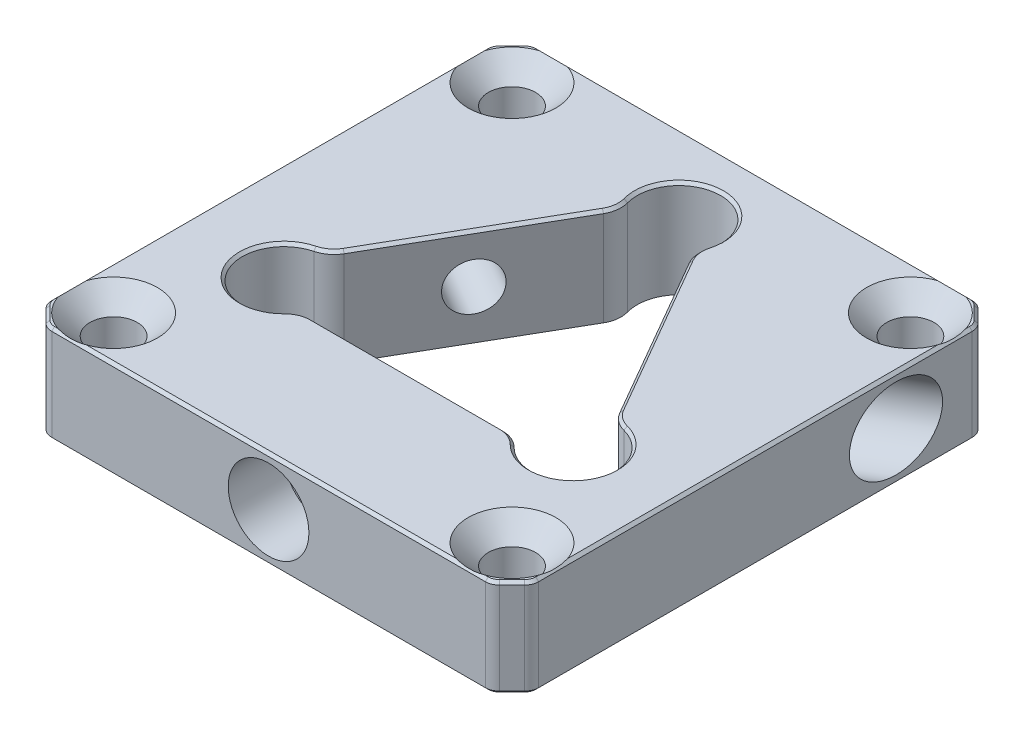
SolidWorks part; units mm, degrees
material "6061 合金"
ref_plane "前视基准面" through (0, 0, 0) normal (0, 0, 1) x (1, 0, 0)
ref_plane "上视基准面" through (0, 0, 0) normal (0, 1, 0) x (1, 0, 0)
ref_plane "右视基准面" through (0, 0, 0) normal (1, 0, 0) x (0, 0, -1)
sketch "草图36" plane through (0, 0, 0) normal (0, 1, 0) x (1, 0, 0)
  line L1 (-17.5, 17.5) -> (17.5, 17.5)
  line L2 (-17.5, 17.5) -> (-17.5, -17.5)
  line L3 (-17.5, -17.5) -> (17.5, -17.5)
  line L4 (17.5, 17.5) -> (17.5, -17.5)
  line L5 (-17.5, 17.5) -> (17.5, -17.5) construction
  line L6 (-17.5, -17.5) -> (17.5, 17.5) construction
  point P0 (0, 0)
  dimension "D1" = 35
  dimension "D2" = 35
extrude "凸台-拉伸8" add sketch "草图36" along normal blind 7
sketch "草图37" plane through (0, 7, 0) normal (0, 1, 0) x (1, 0, 0)
  line L1 (-14.32, 14.32) -> (14.32, 14.32) construction
  line L2 (-14.32, 14.32) -> (-14.32, -14.32) construction
  line L3 (-14.32, -14.32) -> (14.32, -14.32) construction
  line L4 (14.32, 14.32) -> (14.32, -14.32) construction
  line L5 (-14.32, 14.32) -> (14.32, -14.32) construction
  line L6 (-14.32, -14.32) -> (14.32, 14.32) construction
  circle A0 centre (-14.32, 14.32) radius 1
  circle A1 centre (14.32, 14.32) radius 1
  circle A2 centre (14.32, -14.32) radius 1
  circle A3 centre (-14.32, -14.32) radius 1
  point P0 (0, 0)
  point P16 (0, 0)
  dimension "D3" = 2
  dimension "D1" = 28.64
  dimension "D2" = 28.64
  dimension "D4" = 4
extrude "切除-拉伸8" cut sketch "草图37" against normal blind 14
hole_wizard "M3 十字槽半沉头木螺钉的锥形沉头孔2" positions "草图38" profile "草图39" countersink size "M3" standard "GB" end condition through all
sketch "草图38" plane through (0, 7, 0) normal (0, 1, 0) x (1, 0, 0)
  point P0 (-14.32, 14.32)
  point P3 (-14.32, -14.32)
  point P6 (14.32, -14.32)
  point P9 (14.32, 14.32)
sketch "草图39" plane through (-14.32, 7, -14.32) normal (1, 0, 0) x (0, 0, 1)
  line L0 (0, 0) -> (0, 7)
  line L1 (0, 7) -> (1.7, 7)
  line L2 (1.7, 7) -> (1.7, 1.45)
  line L3 (1.7, 1.45) -> (3.15, 0)
  line L5 (3.15, 0) -> (0, 0)
  line L6 (-1.7, 1.45) -> (-3.15, 0) construction
  line L11 (0, -6.35) -> (0, 107.95) construction
  dimension "通孔孔直径" = 3.4
  dimension "通孔孔深度" = 7
  dimension "近端锥形沉头孔直径" = 6.3
  dimension "近端锥形沉头孔角度" = 90
sketch "草图40" plane through (0, 7, 0) normal (0, 1, 0) x (1, 0, 0)
  line L0 (0, 15) -> (-12.9904, -7.5)
  line L1 (-12.9904, -7.5) -> (12.9904, -7.5)
  line L2 (12.9904, -7.5) -> (0, 15)
  circle A0 centre (0, 0) radius 15 construction
  dimension "D1" = 30
extrude "切除-拉伸9" cut sketch "草图40" against normal blind 9
fillet "圆角8" radius 3 3 edges at (12.9904, 3.5, 7.5) (-12.9904, 3.5, 7.5) (0, 3.5, -15)
sketch "草图41" plane through (0, 7, 0) normal (0, 1, 0) x (1, 0, 0)
  circle A0 centre (0, 12) radius 3
  arc A1 (2.5981, 10.5) -> (-2.5981, 10.5) centre (0, 9) ccw construction
  circle A2 centre (10.3923, -6) radius 3
  circle A3 centre (-10.3923, -6) radius 3
  point P12 (0, 0)
  dimension "D1" = 6
  dimension "D2" = 3
extrude "切除-拉伸10" cut sketch "草图41" against normal blind 25.5
chamfer "倒角3" distance 1.5 angle 45 4 edges at (-17.5, 3.5, 17.5) (17.5, 3.5, 17.5) (-17.5, 3.5, -17.5) (17.5, 3.5, -17.5)
fillet "圆角9" radius 1 8 edges at (-17.5, 3.5, 16) (-16, 3.5, 17.5) (16, 3.5, 17.5) (17.5, 3.5, 16) (17.5, 3.5, -16) (16, 3.5, -17.5) (-17.5, 3.5, -16) (-16, 3.5, -17.5)
sketch "草图44" plane through (-6.4952, 0, -3.75) normal (0.866, 0, 0.5) x (0.5, 0, -0.866)
  line L0 (7.7942, 7) -> (-7.7942, 7) construction
  line L1 (0, 7) -> (0, 0) construction
  line L2 (7.7942, 0) -> (-7.7942, 0) construction
  circle A0 centre (0, 3.5) radius 1.7
  dimension "D1" = 3.4
  dimension "D2" = 3.5
extrude "切除-拉伸11" cut sketch "草图44" against normal blind 16
ref_axis "基准轴3" through (0, 61.25, 0) along (0, -1, 0)
pattern_circular "阵列(圆周)4" count 3 over 360 about axis through (0, 61.25, 0) along (0, -1, 0) of "切除-拉伸11"
ref_plane "基准面7" through (-19.4856, 0, -11.25) normal (0.866, 0, 0.5) x (0.5, 0, -0.866)
sketch "草图46" plane through (-19.4856, 0, -11.25) normal (0.866, 0, 0.5) x (0.5, 0, -0.866)
  circle A0 centre (0, 3.5) radius 2.9
  dimension "D1" = 5.8
extrude "切除-拉伸12" cut sketch "草图46" along normal offset from surface (9 mm away) 6 up to face at (-5.6452, 3.5, -5.2222)
ref_plane "基准面8" through (19.4856, 0, -11.25) normal (-0.866, 0, 0.5) x (0.5, 0, 0.866)
sketch "草图47" plane through (19.4856, 0, -11.25) normal (-0.866, 0, 0.5) x (0.5, 0, 0.866)
  circle A0 centre (0, 3.5) radius 2.9
  dimension "D1" = 5.8
extrude "切除-拉伸13" cut sketch "草图47" along normal offset from surface (9 mm away) 6 up to face at (7.3452, 3.5, -2.2778)
sketch "草图48" plane through (0, 0, 17.5) normal (0, 0, 1) x (1, 0, 0)
  circle A0 centre (0, 3.5) radius 2.9
  dimension "D1" = 5.8
extrude "切除-拉伸14" cut sketch "草图48" against normal offset from surface (4 mm away) 6 up to face at (-1.7, 3.5, 7.5)
fillet "圆角10" radius 2 6 edges at (7.7942, 3.5, 7.5) (-7.7942, 3.5, 7.5) (-2.5981, 3.5, -10.5) (-10.3923, 3.5, 3) (10.3923, 3.5, 3) (2.5981, 3.5, -10.5)
sketch "草图49" plane through (0, 0, -17.5) normal (0, 0, -1) x (-1, 0, 0)
  line L0 (-16.2929, 3.5) -> (16.2929, 3.5) construction
  line L2 (16.2929, 7) -> (16.2929, 0) construction
  line L3 (-16.2929, 0) -> (-16.2929, 7) construction
  line L4 (0, 7) -> (0, 0) construction
  line L5 (-15.5858, 7) -> (15.5858, 7) construction
  circle A0 centre (-8, 3.5) radius 1
  circle A1 centre (8, 3.5) radius 1
  dimension "D1" = 2
  dimension "D2" = 8
extrude "切除-拉伸15" cut sketch "草图49" against normal blind 6
hole_wizard "M3 螺纹孔1" positions "草图50" profile "草图52" tap size "M3" standard "GB"
sketch "草图50" plane through (0, 0, -17.5) normal (0, 0, -1) x (-1, 0, 0)
  point P0 (-8, 3.5)
  point P3 (8, 3.5)
sketch "草图52" plane through (8, 3.5, -17.5) normal (1, 0, 0) x (0, 1, 0)
  line L0 (0, 0) -> (0, 7.7511)
  line L1 (0, 7.7511) -> (1.25, 7)
  line L2 (1.25, 7) -> (1.25, 0)
  line L5 (1.25, 0) -> (0, 0)
  line L10 (0, 7.7511) -> (-1.25, 7) construction
  line L11 (0, -6.35) -> (0, 107.95) construction
  dimension "螺纹孔钻头直径" = 2.5
  dimension "螺纹孔钻头深度" = 7
  dimension "导头角度" = 118
cosmetic thread "孔螺纹线1" parameters "D1"=6, "D2"=3
cosmetic thread "孔螺纹线2" parameters "D1"=6, "D2"=3
chamfer "倒角4" distance 0.2 angle 45 32 edges at (0, 0, 17.5) (15.9685, 0, 17.4239) (-15.9685, 0, 17.4239) (16.75, 0, 16.75) (-16.75, 0, 16.75) (17.4239, 0, 15.9685) (-17.4239, 0, 15.9685) (17.5, 0, 0) (-17.5, 0, 0) (17.4239, 0, -15.9685) (-17.4239, 0, -15.9685) (16.75, 0, -16.75) (-16.75, 0, -16.75) (15.9685, 0, -17.4239) (-15.9685, 0, -17.4239) (0, 0, -17.5) (-17.5, 7, 0) (-17.4239, 7, 15.9685) (-17.4239, 7, -15.9685) (-16.75, 7, 16.75) (-16.75, 7, -16.75) (-15.9685, 7, 17.4239) (-15.9685, 7, -17.4239) (0, 7, 17.5) (0, 7, -17.5) (15.9685, 7, 17.4239) (15.9685, 7, -17.4239) (16.75, 7, 16.75) (16.75, 7, -16.75) (17.4239, 7, 15.9685) (17.4239, 7, -15.9685) (17.5, 7, 0)
chamfer "倒角5" distance 0.2 angle 45 12 edges at (12.9904, 7, 7.5) (10.4285, 7, 2.7504) (7.5962, 7, 7.6561) (6.4952, 7, -3.75) (0, 7, 7.5) (2.8323, 7, -10.4065) (-7.5962, 7, 7.6561) (0, 7, -15) (-12.9904, 7, 7.5) (-2.8323, 7, -10.4065) (-10.4285, 7, 2.7504) (-6.4952, 7, -3.75)
